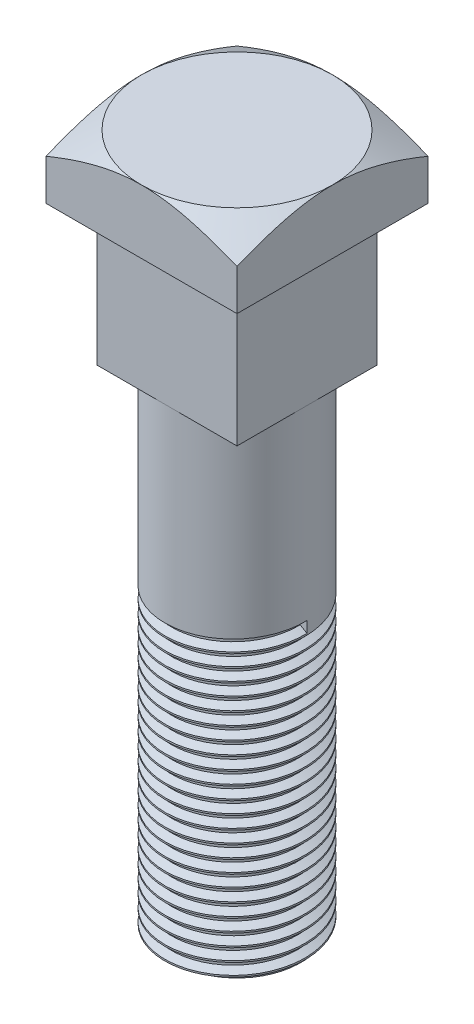
SolidWorks part; units mm, degrees
ref_plane "Front Plane" through (0, 0, 0) normal (0, 0, 1) x (1, 0, 0)
ref_plane "Top Plane" through (0, 0, 0) normal (0, 1, 0) x (1, 0, 0)
ref_plane "Right Plane" through (0, 0, 0) normal (1, 0, 0) x (0, 0, -1)
sketch "Sketch1" plane through (0, 0, 0) normal (0, 1, 0) x (1, 0, 0)
  line L1 (15, -15) -> (-15, -15)
  line L2 (15, -15) -> (15, 15)
  line L3 (15, 15) -> (-15, 15)
  line L4 (-15, -15) -> (-15, 15)
  line L5 (15, -15) -> (-15, 15) construction
  line L6 (15, 15) -> (-15, -15) construction
  point P0 (0, 0)
  dimension "D1" = 30
extrude "Boss-Extrude1" add sketch "Sketch1" against normal blind 10
sketch "Sketch2" plane through (0, 0, 0) normal (0, 1, 0) x (1, 0, 0)
  line L0 (-15, 15) -> (-15, -15) construction
  circle A0 centre (0, 0) radius 15
extrude "Cut-Extrude1" cut sketch "Sketch2" against normal through all draft 60 flip side to cut
sketch "Sketch3" plane through (0, -10, 0) normal (0, -1, 0) x (1, 0, 0)
  line L1 (11, -11) -> (-11, -11)
  line L2 (11, -11) -> (11, 11)
  line L3 (11, 11) -> (-11, 11)
  line L4 (-11, -11) -> (-11, 11)
  line L5 (11, -11) -> (-11, 11) construction
  line L6 (11, 11) -> (-11, -11) construction
  point P0 (0, 0)
  dimension "D1" = 22
extrude "Boss-Extrude2" add sketch "Sketch3" along normal blind 22
sketch "Sketch4" plane through (0, -32, 0) normal (0, -1, 0) x (1, 0, 0)
  circle A0 centre (0, 0) radius 11
  dimension "D1" = 22
extrude "Boss-Extrude3" add sketch "Sketch4" along normal blind 78
sketch "Sketch5" plane through (0, 0, 0) normal (1, 0, 0) x (0, 0, -1)
  line L0 (-11, -32) -> (-11, -110) construction
  line L1 (-11, -110) -> (11, -110) construction
  line L2 (-11, -108) -> (-11, -115.1484)
  line L3 (-11, -115.1484) -> (0, -115.1484)
  line L4 (0, -115.1484) -> (0, -110)
  line L5 (0, -110) -> (0, -102.0655) construction
  arc A0 (-11, -108) -> (0, -110) centre (0, -78.75) ccw
  dimension "D1" = 2
revolve "Cut-Revolve1" cut sketch "Sketch5" angle 360 about L5
thread "Thread1" pitch 2 method cut profile "Thread Profile1" start angle 0, offset 5, length 50, pitch 2, diameter 22
ref_plane "Plane1" through (11, -113, 0) normal (0, 0, 1) x (1, 0, 0)
sketch "Thread Profile1" plane through (11, -113, 0) normal (0, 0, 1) x (1, 0, 0)
  line L0 (0, 0) -> (0, 2) construction
  line L11 (0, 0) -> (0, 1.75)
  line L12 (0, 1.75) -> (-1.0825, 1.125)
  line L13 (-1.0825, 1.125) -> (-1.0825, 0.625)
  line L15 (-1.0825, 0.625) -> (0, 0)
  line L17 (-1.0825, 0.875) -> (0, 0.875) construction
  point P2 (0, 0)
  dimension "Pitch" = 2
  dimension "Profile_Angle" = 60
  dimension "Profile_Land" = 0.5
  dimension "Profile_Height" = 1.0825
